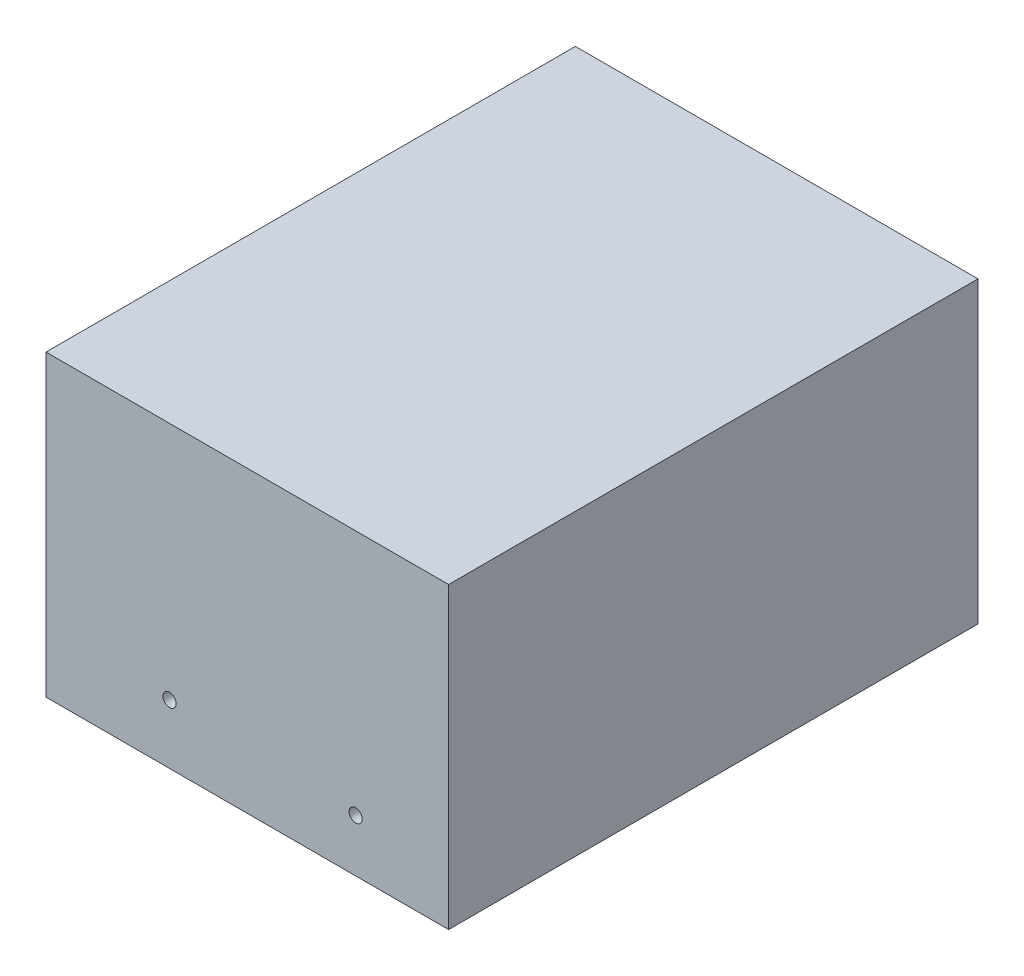
SolidWorks part; units mm, degrees
ref_plane "Front Plane" through (0, 0, 0) normal (0, 0, 1) x (1, 0, 0)
ref_plane "Top Plane" through (0, 0, 0) normal (0, 1, 0) x (1, 0, 0)
ref_plane "Right Plane" through (0, 0, 0) normal (1, 0, 0) x (0, 0, -1)
sketch "Sketch1" plane through (0, 0, 0) normal (0, 0, 1) x (1, 0, 0)
  line L0 (0, 0) -> (48.9, 0)
  line L1 (48.9, 0) -> (48.9, -36.3)
  line L2 (48.9, -36.3) -> (0, -36.3)
  line L3 (0, -36.3) -> (0, 0)
  dimension "D1" = 48.9
  dimension "D2" = 36.3
extrude "Boss-Extrude1" add sketch "Sketch1" along normal blind 26
sketch "Sketch3" plane through (0, 0, 0) normal (0, 0, -1) x (-1, 0, 0)
  line L0 (-48.9, -18.15) -> (-46.92, -18.15) construction
  line L1 (-48.9, -36.3) -> (-48.9, 0) construction
  line L2 (0, -18.15) -> (-1.98, -18.15) construction
  line L3 (0, 0) -> (0, -36.3) construction
  line L4 (-24.45, 0) -> (-24.45, -1.98) construction
  line L5 (-48.9, 0) -> (0, 0) construction
  line L6 (-24.45, -36.3) -> (-24.45, -34.32) construction
  line L7 (0, -36.3) -> (-48.9, -36.3) construction
  line L8 (-24.45, -1.98) -> (-46.92, -1.98)
  line L9 (-46.92, -1.98) -> (-46.92, -34.32)
  line L10 (-46.92, -34.32) -> (-1.98, -34.32)
  line L11 (-1.98, -34.32) -> (-1.98, -1.98)
  line L12 (-1.98, -1.98) -> (-24.45, -1.98)
  dimension "D1" = 1.98
  dimension "D2" = 1.98
  dimension "D3" = 1.98
  dimension "D4" = 1.98
extrude "Cut-Extrude1" cut sketch "Sketch3" against normal blind 24.5
sketch "Sketch4" plane through (0, 0, 24.5) normal (0, 0, -1) x (-1, 0, 0)
  line L8 (-46.92, -34.32) -> (-1.98, -34.32) construction
  line L9 (-39.66, -1.98) -> (-37.51, -1.98)
  line L10 (-1.98, -1.98) -> (-46.92, -1.98) construction
  line L11 (-37.51, -1.98) -> (-37.51, -4.33)
  line L12 (-37.51, -4.33) -> (-39.66, -4.33)
  line L13 (-39.66, -4.33) -> (-39.66, -1.98)
  line L14 (-46.92, -1.98) -> (-46.92, -34.32) construction
  line L16 (-37.51, -1.98) -> (-30.56, -1.98) construction
  line L17 (-30.56, -1.98) -> (-30.56, -4.33)
  line L18 (-30.56, -4.33) -> (-28.41, -4.33)
  line L19 (-28.41, -4.33) -> (-28.41, -1.98)
  line L20 (-28.41, -1.98) -> (-30.56, -1.98)
  line L21 (-28.41, -1.98) -> (-21.46, -1.98) construction
  line L22 (-21.46, -1.98) -> (-21.46, -4.33)
  line L23 (-21.46, -4.33) -> (-19.31, -4.33)
  line L24 (-19.31, -4.33) -> (-19.31, -1.98)
  line L25 (-19.31, -1.98) -> (-21.46, -1.98)
  line L26 (-19.31, -1.98) -> (-12.36, -1.98) construction
  line L27 (-12.36, -1.98) -> (-12.36, -4.33)
  line L28 (-12.36, -4.33) -> (-10.21, -4.33)
  line L29 (-10.21, -4.33) -> (-10.21, -1.98)
  line L30 (-10.21, -1.98) -> (-12.36, -1.98)
  dimension "D3" = 7.26
  dimension "D4" = 2.15
  dimension "D5" = 2.35
  dimension "D6" = 6.95
  dimension "D7" = 2.15
  dimension "D8" = 6.95
  dimension "D9" = 2.15
  dimension "D10" = 6.95
  dimension "D11" = 2.15
  dimension "D12" = 2.35
  dimension "D13" = 2.35
  dimension "D14" = 2.35
extrude "Boss-Extrude3" add sketch "Sketch4" along normal up to surface (24.5 mm away) up to face at (24.45, -18.15, 0)
sketch "Sketch5" plane through (0, 0, 24.5) normal (0, 0, -1) x (-1, 0, 0)
  line L0 (-46.92, -34.32) -> (-1.98, -34.32) construction
  line L1 (-11.04, -17.37) -> (-37.86, -17.37)
  line L2 (-11.04, -17.37) -> (-11.04, -20.32)
  line L3 (-11.04, -20.32) -> (-37.86, -20.32)
  line L4 (-37.86, -17.37) -> (-37.86, -20.32)
  line L5 (-11.04, -17.37) -> (-37.86, -20.32) construction
  line L6 (-11.04, -20.32) -> (-37.86, -17.37) construction
  point P0 (-24.45, -18.15)
  dimension "D1" = 26.82
  dimension "D2" = 2.95
  dimension "D3" = 14
extrude "Boss-Extrude4" add sketch "Sketch5" along normal blind 16.12
sketch "Sketch6" plane through (0, 0, 8.38) normal (0, 0, -1) x (-1, 0, 0)
  line L0 (-37.86, -20.32) -> (-35.49, -20.32) construction
  line L1 (-37.86, -20.32) -> (-11.04, -20.32) construction
  line L3 (-35.49, -20.32) -> (-35.49, -19.58)
  line L4 (-35.49, -19.58) -> (-30.92, -19.58)
  line L5 (-30.92, -19.58) -> (-30.92, -20.32)
  line L6 (-30.92, -20.32) -> (-35.49, -20.32)
  line L7 (-30.92, -20.32) -> (-28.55, -20.32) construction
  line L11 (-20.55, -20.32) -> (-28.55, -20.32)
  line L12 (-24.45, -17.37) -> (-24.45, -24.8823) construction
  line L13 (-11.04, -17.37) -> (-37.86, -17.37) construction
  line L14 (-17.98, -20.32) -> (-13.41, -20.32)
  line L15 (-13.41, -20.32) -> (-13.41, -19.58)
  line L16 (-17.98, -19.58) -> (-17.98, -20.32)
  line L17 (-13.41, -19.58) -> (-17.98, -19.58)
  line L18 (-37.86, -18.845) -> (-11.04, -18.845) construction
  line L19 (-37.86, -17.37) -> (-37.86, -20.32) construction
  line L20 (-11.04, -20.32) -> (-11.04, -17.37) construction
  line L21 (-13.41, -17.37) -> (-13.41, -18.11)
  line L22 (-13.41, -18.11) -> (-17.98, -18.11)
  line L23 (-17.98, -17.37) -> (-13.41, -17.37)
  line L24 (-17.98, -18.11) -> (-17.98, -17.37)
  line L27 (-20.55, -17.37) -> (-28.55, -17.37)
  line L29 (-30.92, -18.11) -> (-30.92, -17.37)
  line L30 (-30.92, -17.37) -> (-35.49, -17.37)
  line L31 (-35.49, -18.11) -> (-30.92, -18.11)
  line L32 (-35.49, -17.37) -> (-35.49, -18.11)
  line L33 (-28.55, -20.32) -> (-28.55, -19.58)
  line L34 (-28.55, -19.58) -> (-20.55, -19.58)
  line L35 (-20.55, -19.58) -> (-20.55, -20.32)
  line L36 (-28.55, -17.37) -> (-28.55, -18.11)
  line L37 (-28.55, -18.11) -> (-20.55, -18.11)
  line L38 (-20.55, -18.11) -> (-20.55, -17.37)
  dimension "D1" = 2.37
  dimension "D2" = 0.74
  dimension "D3" = 4.57
  dimension "D4" = 2.37
extrude "Cut-Extrude2" cut sketch "Sketch6" against normal blind 16.12
sketch "Sketch7" plane through (48.9, 0, 0) normal (1, 0, 0) x (0, 0, -1)
  line L0 (-26, 0) -> (-64.3, 0)
  line L1 (-64.3, 0) -> (-64.3, -36.3)
  line L2 (-64.3, -36.3) -> (-26, -36.3)
  line L3 (-26, -36.3) -> (-26, 0)
  dimension "D1" = 38.3
extrude "Boss-Extrude5" add sketch "Sketch7" against normal up to surface (48.9 mm away) up to face at (0, -18.15, 13)
sketch "Sketch8" plane through (0, 0, 24.5) normal (0, 0, -1) x (-1, 0, 0)
  circle A0 centre (-37.6114, -29.9288) radius 0.9
  circle A1 centre (-15.011, -29.088) radius 0.9
  dimension "D1" = 1.8
  dimension "D2" = 1.8
extrude "Cut-Extrude3" cut sketch "Sketch8" against normal blind 11.45
sketch "Sketch9" plane through (0, 0, 35.95) normal (0, 0, -1) x (-1, 0, 0)
  circle A0 centre (-37.6114, -29.9288) radius 0.8
  circle A1 centre (-15.011, -29.088) radius 0.8
  dimension "D1" = 1.6
  dimension "D2" = 1.6
extrude "Cut-Extrude4" cut sketch "Sketch9" against normal through all
sketch "Croquis1" plane through (0, 0, 0) normal (0, 0, -1) x (-1, 0, 0)
  line L0 (0, -36.3) -> (0, -31.3) construction
  line L1 (0, 0) -> (0, -36.3) construction
  line L3 (0, -31.3) -> (3, -31.3)
  line L4 (0, -31.3) -> (0, -33.8)
  line L5 (0, -33.8) -> (3, -33.8)
  line L6 (3, -31.3) -> (3, -33.8)
  dimension "D1" = 5
  dimension "D2" = 3
extrude "Saliente-Extruir1" add sketch "Croquis1" against normal blind 3
sketch "Croquis2" plane through (0, 0, 0) normal (0, 0, -1) x (-1, 0, 0)
  circle A0 centre (1.5, -32.55) radius 0.75
  dimension "D1" = 1.5
extrude "Cortar-Extruir1" cut sketch "Croquis2" against normal blind 3
